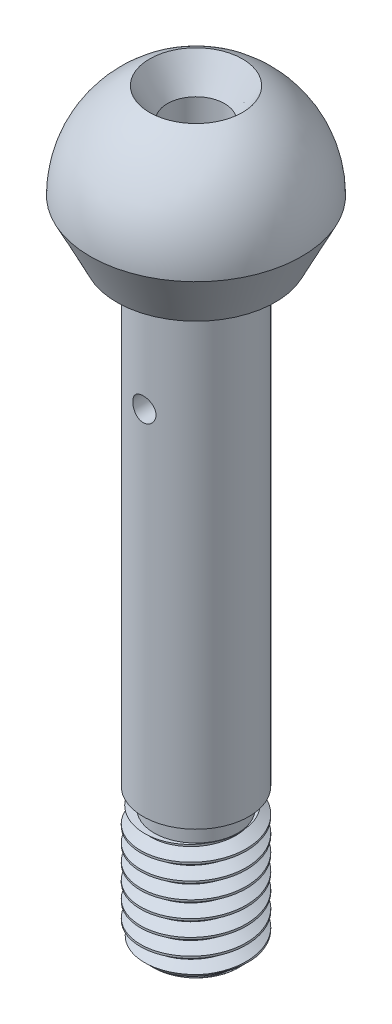
SolidWorks part; units mm, degrees
ref_plane "Front Plane" through (0, 0, 0) normal (0, 0, 1) x (1, 0, 0)
ref_plane "Top Plane" through (0, 0, 0) normal (0, 1, 0) x (1, 0, 0)
ref_plane "Right Plane" through (0, 0, 0) normal (1, 0, 0) x (0, 0, -1)
sketch "Sketch2" plane through (0, 0, 0) normal (0, 0, 1) x (1, 0, 0)
  line L0 (0, 12.7) -> (0, -77.7875)
  line L1 (12.7, 0) -> (9.525, 0) construction
  line L2 (0, 0) -> (9.525, 0) construction
  line L3 (12.7, 0) -> (9.525, -6.35)
  line L5 (9.525, 0) -> (9.525, -6.35) construction
  line L6 (9.525, -6.35) -> (6.35, -6.35)
  line L7 (6.35, -6.35) -> (6.35, -77.7875)
  line L8 (6.35, -77.7875) -> (0, -77.7875)
  arc A0 (12.7, 0) -> (0, 12.7) centre (0, 0) ccw
  dimension "D1" = 12.7
  dimension "D4" = 6.35
  dimension "D5" = 3.175
revolve "Revolve2" add sketch "Sketch2" angle 360 about L0
ref_plane "Plane1" through (0, 12.7, 0) normal (0, 1, 0) x (1, 0, 0)
sketch "Sketch6" plane through (0, 12.7, 0) normal (0, 1, 0) x (1, 0, 0)
  circle A0 centre (0, 0) radius 6.35
extrude "Cut-Extrude2" cut sketch "Sketch6" against normal blind 5.08 draft 31
ref_plane "Plane2" through (0, 0, 12.7) normal (0, 0, 1) x (1, 0, 0)
sketch "Sketch7" plane through (0, 0, 12.7) normal (0, 0, 1) x (1, 0, 0)
  circle A0 centre (0, -19.05) radius 1.397
  dimension "D1" = 19.05
extrude "Cut-Extrude3" cut sketch "Sketch7" against normal through all contours A0
sketch "Sketch8" plane through (0, 7.62, 0) normal (0, 1, 0) x (1, 0, 0)
  circle A0 centre (0, 0) radius 3.429
  dimension "D1" = 6.858
extrude "Cut-Extrude4" cut sketch "Sketch8" against normal blind 31.75 and the other way through all
chamfer "Chamfer1" distance 1.27 angle 45 1 edges at (-6.35, -77.7875, 0)
sketch "Sketch10" plane through (0, -77.7875, 0) normal (0, -1, 0) x (1, 0, 0)
  circle A0 centre (0, 0) radius 6.35
curve "Helix/Spiral1" pitch 1.9538 height 15.6308 radius 6.35 centre (0, -77.7875, 0) axis (0, 1, 0) start towards (0, 0, 1)
sketch "Sketch11" plane through (0, 0, 0) normal (1, 0, 0) x (0, 0, -1)
  line L0 (-6.35, -77.0543) -> (-6.35, -79.0081) construction
  line L1 (-6.35, -79.0081) -> (-6.35, -78.7644) construction
  line L2 (-6.35, -78.7644) -> (-6.944, -78.7644)
  line L3 (-6.35, -78.7644) -> (-5.08, -78.0312)
  line L4 (-5.08, -78.0312) -> (-5.08, -77.7875)
  line L5 (-5.08, -77.7875) -> (-6.35, -77.0543)
  line L6 (-6.944, -78.7644) -> (-6.944, -77.0543)
  line L7 (-6.944, -77.0543) -> (-6.35, -77.0543)
  line L8 (-5.08, -77.7875) -> (5.08, -77.7875) construction
  line L19 (-6.35, -20.447) -> (-6.35, -76.5175) construction
  dimension "D1" = 1.9538
  dimension "D2" = 60
  dimension "D3" = 60
  dimension "D4" = 1.27
sweep "Cut-Sweep2" cut profiles "Sketch11" path "Helix/Spiral1"
sketch "Sketch12" plane through (0, 0, 0) normal (-1, 0, 0) x (0, 0, 1)
  line L2 (5.0165, -61.4235) -> (7.6835, -61.4235)
  line L3 (5.0165, -61.4235) -> (5.0165, -63.8047)
  line L4 (5.0165, -63.8047) -> (7.6835, -63.8047)
  line L5 (7.6835, -61.4235) -> (7.6835, -63.8047)
  point P0 (6.35, -61.4235)
  dimension "D1" = 2.667
  dimension "D2" = 2.3813
revolve "Cut-Revolve1" cut sketch "Sketch12" angle 360 about axis through (0, 12.7, 0) along (0, 1, 0)
